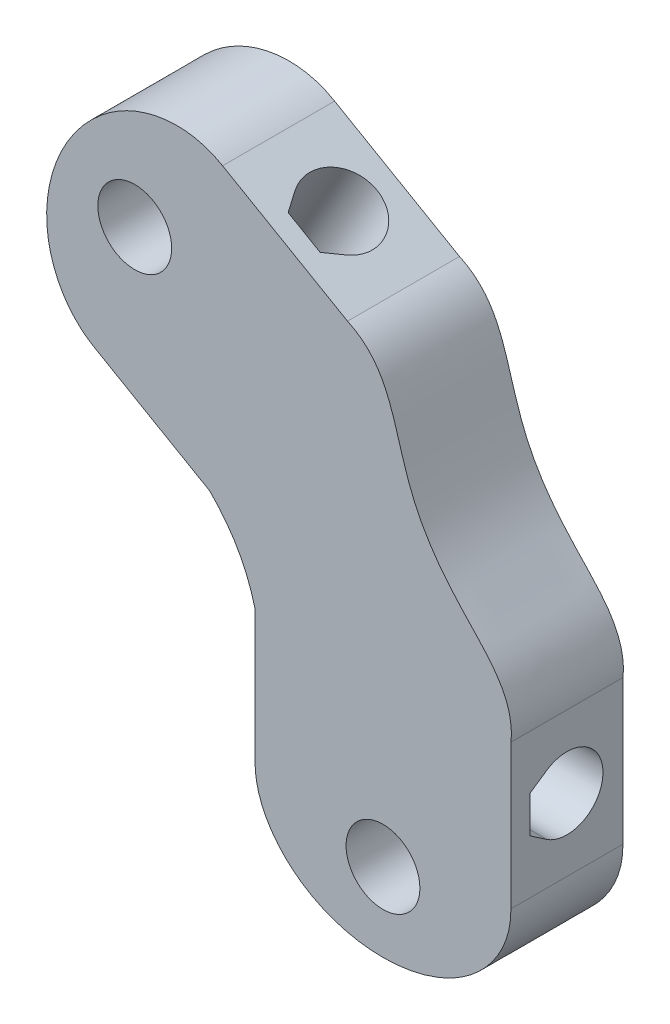
SolidWorks part; units mm, degrees
ref_plane "Piano frontale" through (0, 0, 0) normal (0, 0, 1) x (1, 0, 0)
ref_plane "Piano superiore" through (0, 0, 0) normal (0, 1, 0) x (1, 0, 0)
ref_plane "Piano destro" through (0, 0, 0) normal (1, 0, 0) x (0, 0, -1)
sketch "Model" plane through (0, 0, 0) normal (0, 0, 1) x (1, 0, 0)
  line L0 (-32.3853, 85.015) -> (-17.6641, 76.516)
  line L1 (-47.4603, 58.9044) -> (-33.9142, 51.0835)
  line L2 (-28.5624, 41.7237) -> (-28.5624, 26.1722)
  line L3 (1.5876, 43.1722) -> (1.5876, 26.1722)
  line L4 (-15.8086, 58.4351) -> (-23.9493, 53.7351)
  line L5 (-23.9493, 53.7351) -> (-22.6493, 51.4834)
  line L6 (-22.6493, 51.4834) -> (-29.3258, 52.2475)
  line L7 (-29.3258, 52.2475) -> (-26.5993, 58.325)
  line L8 (-26.5993, 58.325) -> (-25.2993, 56.0734)
  line L9 (-25.2993, 56.0734) -> (-17.1586, 60.7734)
  line L10 (-17.1586, 60.7734) -> (-15.8086, 58.4351)
  line L11 (-18.3993, 44.1222) -> (-25.0758, 44.8863)
  line L12 (-25.0758, 44.8863) -> (-22.3493, 50.9638)
  line L13 (-22.3493, 50.9638) -> (-21.0493, 48.7121)
  line L14 (-21.0493, 48.7121) -> (-12.9086, 53.4122)
  line L15 (-12.9086, 53.4122) -> (-11.5086, 50.9873)
  line L16 (-11.5086, 50.9873) -> (-19.6493, 46.2873)
  line L17 (-19.6493, 46.2873) -> (-18.3993, 44.1222)
  line L18 (-7.6874, 50.7686) -> (-10.0256, 49.4186)
  line L19 (-10.0256, 49.4186) -> (-17.8756, 63.0152)
  line L20 (-17.8756, 63.0152) -> (-15.5374, 64.3652)
  line L21 (-15.5374, 64.3652) -> (-7.6874, 50.7686)
  circle A0 centre (-13.4874, 22.9222) radius 4.35
  circle A1 centre (-42.7374, 73.5847) radius 4.35
  spline S0 degree 3 poles (-32.3853, 85.015) (-35.6002, 86.9166) (-41.474, 86.6984) (-47.5594, 82.6446) (-50.9721, 78.3607) (-52.9853, 73.2681) (-53.4757, 65.9598) (-50.71, 60.7543) (-47.4603, 58.9044) knots 0 0 0 0 0.249338 0.374428 0.499621 0.624814 0.749906 1 1 1 1
  spline S1 degree 3 poles (-17.6641, 76.516) (-13.8887, 74.7963) (-12.1809, 69.346) (-10.1387, 62.3226) (-7.342, 57.3703) (-2.3112, 51.7096) (2.0516, 47.5864) (1.5876, 43.1722) knots 0 0 0 0 0.279425 0.419812 0.560237 0.70731 1 1 1 1
  spline S2 degree 3 poles (1.5876, 26.1722) (1.6269, 22.4337) (-1.5043, 17.4528) (-8.0658, 14.2116) (-13.4874, 13.4024) (-18.9089, 14.2116) (-25.4704, 17.4528) (-28.6017, 22.4338) (-28.5624, 26.1722) knots 0 0 0 0 0.249526 0.374712 0.5 0.625288 0.750474 1 1 1 1
  spline S3 degree 2 poles (-33.9142, 51.0835) (-29.9422, 47.1736) (-28.5624, 41.7237) knots 0 0 0 1 1 1
extrude "Main body" add sketch "Model" along normal blind 13.2 contours L1 S3 L2 S2 L3 S1 L0 S0 | A0 | A1
extrude "Side up graphic" cut sketch "Model<4>" along normal blind 1 contours L10 L9 L8 L7 L6 L5 L4 | L14 L15 L16 L17 L11 L12 L13 | L19 L20 L21 L18 region at (-23.1283, 55.7767, 0)
sketch "Model<4>" plane through (0, 0, 0) normal (0, 0, 1) x (1, 0, 0) same geometry as "Model"
sketch "Schizzo3" plane through (1.5876, 0, 0) normal (1, 0, 0) x (0, 0, -1)
  line L0 (0, 34.6722) -> (-13.2, 34.6722) construction
  line L1 (0, 43.1722) -> (0, 26.1722) construction
  line L2 (-13.2, 43.1722) -> (-13.2, 26.1722) construction
  line L3 (-10.95, 32.4972) -> (-10.95, 36.8472)
  line L4 (-10.95, 32.4972) -> (-8.9978, 31.1632)
  line L5 (-10.95, 36.8472) -> (-8.9978, 38.1812)
  arc A0 (-8.9978, 31.1632) -> (-8.9978, 38.1812) centre (-6.6, 34.6722) ccw
  point P9 (-10.95, 34.6722)
  dimension "D3" = 8.5
  dimension "D1" = 4.35
  dimension "D2" = 2.25
extrude "Hole 1" cut sketch "Schizzo3" against normal up to next
sketch "Schizzo4" plane through (28.7161, 49.7391, 0) normal (0.5, 0.866, 0) x (0.866, -0.5, 0)
  line L0 (-62.0541, 0) -> (-62.0541, -13.2) construction
  line L1 (-70.5533, 0) -> (-53.5549, 0) construction
  line L2 (-70.5533, -13.2) -> (-53.5549, -13.2) construction
  line L3 (-64.2291, -10.95) -> (-59.8791, -10.95)
  line L4 (-64.2291, -10.95) -> (-65.5631, -8.9978)
  line L5 (-59.8791, -10.95) -> (-58.5451, -8.9978)
  arc A0 (-58.5451, -8.9978) -> (-65.5631, -8.9978) centre (-62.0541, -6.6) ccw
  point P11 (-62.0541, -10.95)
  dimension "D1" = 8.5
  dimension "D2" = 2.25
  dimension "D3" = 4.35
extrude "Hole 2" cut sketch "Schizzo4" against normal up to next contours A0 L4 L3 L5
ref_axis "Screwhole 1" through (-42.7374, 73.5847, 13.2) along (0, 0, -1)
ref_axis "Screwhole 2" through (-13.4874, 22.9222, 13.2) along (0, 0, -1)
ref_axis "Screwhole 3" through (-28.5624, 34.6722, 6.6) along (1, 0, 0)
ref_axis "Screwhole 4" through (-41.9397, 51.4671, 6.6) along (0.5, 0.866, 0)
